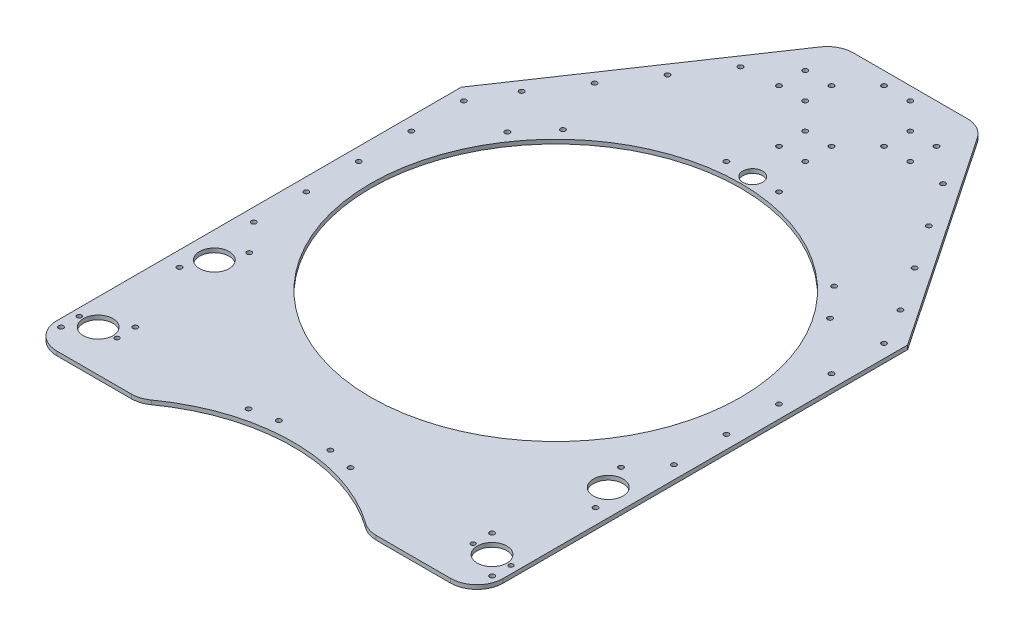
SolidWorks part; units mm, degrees
material "Thornel Mat VMA"
ref_plane "Front Plane" through (0, 0, 0) normal (0, 0, 1) x (1, 0, 0)
ref_plane "Top Plane" through (0, 0, 0) normal (0, 1, 0) x (1, 0, 0)
ref_plane "Right Plane" through (0, 0, 0) normal (1, 0, 0) x (0, 0, -1)
sketch "Sketch1" plane through (0, 0, 0) normal (0, 1, 0) x (1, 0, 0)
  line L1 (-215.9, 342.9) -> (215.9, 342.9)
  line L2 (-215.9, 342.9) -> (-215.9, -342.9)
  line L3 (-215.9, -342.9) -> (215.9, -342.9)
  line L4 (215.9, 342.9) -> (215.9, -342.9)
  line L5 (-215.9, 342.9) -> (215.9, -342.9) construction
  line L6 (-215.9, -342.9) -> (215.9, 342.9) construction
  point P0 (0, 0)
  dimension "D1" = 431.8
  dimension "D2" = 685.8
extrude "Boss-Extrude1" add sketch "Sketch1" along normal blind 4
sketch "Sketch2" plane through (0, 4, 0) normal (0, 1, 0) x (1, 0, 0)
  line L0 (0, -342.9) -> (0, 342.9) construction
  line L1 (-215.9, -342.9) -> (215.9, -342.9) construction
  line L2 (215.9, 342.9) -> (-215.9, 342.9) construction
  line L3 (-215.9, 342.9) -> (-215.9, -342.9) construction
  line L4 (-208.4605, -320.8555) -> (-190.5, -302.895) construction
  line L5 (-193.1461, -302.895) -> (-215.9, -302.895) construction
  line L6 (190.5, -215.9) -> (190.5, -165.1) construction
  line L7 (190.5, -190.5) -> (201.2345, -213.5202) construction
  line L8 (201.2345, -213.5202) -> (179.7655, -167.4798) construction
  line L9 (-208.4605, -320.8555) -> (-172.5395, -284.9345) construction
  circle A0 centre (-190.5, -302.895) radius 14.3129
  circle A1 centre (-190.5, -190.5) radius 14.3129
  circle A3 centre (190.5, -190.5) radius 14.3129
  circle A4 centre (190.5, -190.5) radius 25.4 construction
  circle A5 centre (-190.5, -190.5) radius 25.4 construction
  circle A6 centre (201.2345, -213.5202) radius 2.3812
  circle A7 centre (179.7655, -167.4798) radius 2.3813
  circle A10 centre (-190.5, -302.895) radius 25.4 construction
  circle A11 centre (-208.4605, -320.8555) radius 2.3813
  circle A15 centre (-172.5395, -284.9345) radius 2.3813
  circle A16 centre (172.5395, -284.9345) radius 2.3813
  circle A17 centre (208.4605, -320.8555) radius 2.3813
  circle A18 centre (190.5, -302.895) radius 14.3129
  circle A19 centre (-179.7655, -167.4798) radius 2.3813
  circle A20 centre (-201.2345, -213.5202) radius 2.3813
  circle A21 centre (208.788, -302.895) radius 2.159
  circle A22 centre (172.212, -302.895) radius 2.159
  circle A23 centre (-172.212, -302.895) radius 2.159
  circle A24 centre (-208.788, -302.895) radius 2.159
  point P33 (-190.5, -304.8)
  point P34 (-189.5475, -303.8475)
  point P48 (190.5, -302.895)
  dimension "D1" = 28.6258
  dimension "D2" = 28.6258
  dimension "D6" = 50.8
  dimension "D7" = 50.8
  dimension "D8" = 4.7625
  dimension "D9" = 4.7625
  dimension "D10" = 18.288
  dimension "D11" = 4.318
  dimension "D12" = 50.8
  dimension "D13" = 4.7625
  dimension "D3" = 40.005
  dimension "D4" = 112.395
  dimension "D5" = 25.4
  dimension "D15" = 45
  dimension "D16" = 25
  dimension "D14" = 2
  dimension "D17" = 2
extrude "Cut-Extrude1" cut sketch "Sketch2" against normal through all
sketch "Sketch3" plane through (0, 0, 0) normal (0, -1, 0) x (-1, 0, 0)
  line L1 (29.8706, 270.2084) -> (-24.7394, 270.2084)
  line L2 (29.8706, 270.2084) -> (29.8706, 216.2334)
  line L3 (29.8706, 216.2334) -> (-24.7394, 216.2334)
  line L4 (-24.7394, 270.2084) -> (-24.7394, 216.2334)
  line L5 (29.8706, 270.2084) -> (-24.7394, 216.2334) construction
  line L6 (29.8706, 216.2334) -> (-24.7394, 270.2084) construction
  point P0 (2.5656, 243.2209)
  dimension "D1" = 53.975
  dimension "D2" = 54.61
extrude "Boss-Extrude2" [suppressed] add sketch "Sketch3" along normal blind 203.2
fillet "Fillet1" [suppressed] radius 20.32
sketch "Sketch4" [suppressed] plane through (0, -203.2, 0) normal (0, -1, 0) x (-1, 0, 0)
  line L0 (-24.7394, 216.2334) -> (29.8706, 216.2334) construction
  line L1 (26.6956, 267.0334) -> (-21.5644, 267.0334)
  line L2 (26.6956, 267.0334) -> (26.6956, 219.4084)
  line L3 (26.6956, 219.4084) -> (-21.5644, 219.4084)
  line L4 (-21.5644, 267.0334) -> (-21.5644, 219.4084)
  line L5 (26.6956, 267.0334) -> (-21.5644, 219.4084) construction
  line L6 (26.6956, 219.4084) -> (-21.5644, 267.0334) construction
  line L7 (29.8706, 270.2084) -> (-24.7394, 270.2084) construction
  line L8 (29.8706, 216.2334) -> (29.8706, 270.2084) construction
  line L9 (-24.7394, 270.2084) -> (-24.7394, 216.2334) construction
  point P0 (2.5656, 243.2209)
  dimension "D1" = 3.175
  dimension "D2" = 3.175
  dimension "D3" = 3.175
  dimension "D4" = 3.175
extrude "Cut-Extrude2" [suppressed] cut sketch "Sketch4" against normal blind 203.2
sketch "Sketch5" [suppressed] plane through (-29.8706, 0, 0) normal (-1, 0, 0) x (0, 0, 1)
  line L0 (-216.2334, -203.2) -> (-216.2334, 0) construction
  line L1 (-216.2334, -203.2) -> (-270.2084, -203.2) construction
  circle A0 centre (-243.2209, -184.15) radius 14.2875
  dimension "D1" = 28.575
  dimension "D2" = 26.9875
  dimension "D3" = 19.05
extrude "Cut-Extrude3" [suppressed] cut sketch "Sketch5" against normal blind 203.2
sketch "Sketch6" plane through (0, 4, 0) normal (0, 1, 0) x (1, 0, 0)
  circle A0 centre (0, -50.8) radius 179.07
  dimension "D1" = 358.14
  dimension "D2" = 50.8
extrude "Cut-Extrude4" cut sketch "Sketch6" against normal through all
sketch "Sketch8" plane through (0, 4, 0) normal (0, 1, 0) x (1, 0, 0)
  circle A0 centre (0, 139.7) radius 9.525
  circle A2 centre (0, 139.7) radius 25.4 construction
  circle A3 centre (25.4, 139.7) radius 2.3813
  circle A4 centre (-25.4, 139.7) radius 2.3813
  dimension "D1" = 19.05
  dimension "D3" = 50.8
  dimension "D4" = 4.7625
  dimension "D5" = 4.7625
  dimension "D2" = 139.7
extrude "Cut-Extrude6" cut sketch "Sketch8" against normal through all
fillet "Fillet2" radius 25.4 2 edges at (215.9, 2, 342.9) (-215.9, 2, 342.9)
sketch "Sketch10" plane through (0, 4, 0) normal (0, 1, 0) x (1, 0, 0)
  line L0 (-215.9, 342.9) -> (-215.9, -317.5) construction
  line L1 (215.9, -317.5) -> (215.9, 342.9) construction
  circle A0 centre (-190.5, 215.9) radius 14.3129
  circle A1 centre (190.5, 215.9) radius 14.3129
  circle A2 centre (-190.5, 215.9) radius 25.4 construction
  circle A3 centre (190.5, 215.9) radius 25.4 construction
  circle A4 centre (190.5, 190.5) radius 2.3813
  circle A5 centre (190.5, 241.3) radius 2.3813
  circle A6 centre (-190.5, 190.5) radius 2.3813
  circle A7 centre (-190.5, 241.3) radius 2.3813
  circle A8 centre (190.5, -190.5) radius 14.3129 construction
  circle A9 centre (-190.5, -190.5) radius 14.3129 construction
  dimension "D1" = 28.6258
  dimension "D2" = 50.8
  dimension "D3" = 28.6258
  dimension "D4" = 50.8
  dimension "D5" = 4.7625
  dimension "D6" = 4.7625
  dimension "D7" = 4.7625
  dimension "D8" = 4.7625
  dimension "D9" = 25.4
  dimension "D10" = 25.4
  dimension "D11" = 406.4
  dimension "D12" = 406.4
extrude "Cut-Extrude8" [suppressed] cut sketch "Sketch10" against normal through all
sketch "Sketch11" plane through (0, 4, 0) normal (0, 1, 0) x (1, 0, 0)
  line L0 (0, -50.8) -> (156.0485, 58.4663) construction
  line L6 (0, 0) -> (0, 139.7) construction
  circle A0 centre (0, -50.8) radius 179.07
  circle A1 centre (0, -50.8) radius 179.07 construction
  circle A2 centre (0, -50.8) radius 184.15
  circle A3 centre (0, -50.8) radius 215.9
  circle A4 centre (156.0485, 58.4663) radius 2.3813
  circle A5 centre (131.1838, 87.3342) radius 2.3813
  circle A6 centre (0, -50.8) radius 190.5 construction
  circle A7 centre (-131.1838, 87.3342) radius 2.3813
  circle A8 centre (-156.0485, 58.4663) radius 2.3813
  dimension "D1" = 368.3
  dimension "D6" = 431.8
  dimension "D7" = 381
  dimension "D9" = 4.7625
  dimension "D10" = 4.7625
  dimension "D2" = 55
  dimension "D8" = 38.1
extrude "Cut-Extrude9" cut sketch "Sketch11" against normal through all contours A4 | A5 | A7 | A8 region at (156.0485, 4, -58.4663) region at (131.1838, 4, -87.3342) region at (-131.1838, 4, -87.3342) region at (-156.0485, 4, -58.4663)
sketch "Sketch13" plane through (0, 4, 0) normal (0, 1, 0) x (1, 0, 0)
  line L0 (-215.9, 342.9) -> (-215.9, -317.5) construction
  line L1 (215.9, 342.9) -> (-215.9, 342.9) construction
  line L2 (0, -342.9) -> (0, 342.9) construction
  line L3 (-190.5, -342.9) -> (190.5, -342.9) construction
  circle A0 centre (-203.2, 317.5) radius 2.3813
  circle A1 centre (-203.2, 266.7) radius 2.3813
  circle A2 centre (-203.2, 215.9) radius 2.3813
  circle A3 centre (-203.2, 165.1) radius 2.3813
  circle A4 centre (-203.2, 114.3) radius 2.3813
  circle A5 centre (-203.2, 63.5) radius 2.3813
  circle A6 centre (-203.2, 12.7) radius 2.3813
  circle A7 centre (-203.2, -38.1) radius 2.3813
  circle A8 centre (-203.2, -88.9) radius 2.3813
  circle A9 centre (-203.2, -139.7) radius 2.3813
  circle A10 centre (203.2, -139.7) radius 2.3813
  circle A11 centre (203.2, 12.7) radius 2.3813
  circle A12 centre (203.2, 63.5) radius 2.3813
  circle A13 centre (203.2, 114.3) radius 2.3813
  circle A14 centre (203.2, 165.1) radius 2.3813
  circle A15 centre (203.2, 266.7) radius 2.3813
  circle A16 centre (203.2, 317.5) radius 2.3813
  circle A17 centre (-25.4, -330.2) radius 2.4664
  circle A20 centre (-50.8, -330.2) radius 2.3078
  circle A21 centre (50.8, -330.2) radius 2.3078
  circle A22 centre (25.4, -330.2) radius 2.4664
  circle A23 centre (203.2, -88.9) radius 2.3813
  circle A24 centre (203.2, -38.1) radius 2.3813
  circle A25 centre (203.2, 215.9) radius 2.3813
  dimension "D1" = 4.7625
  dimension "D2" = 12.7
  dimension "D3" = 25.4
  dimension "D5" = 25.4
  dimension "D6" = 50.8
  dimension "D7" = 12.7
  dimension "D8" = 12.7
  dimension "D4" = 10
extrude "Cut-Extrude10" cut sketch "Sketch13" against normal through all
sketch "Sketch14" plane through (0, 4, 0) normal (0, 1, 0) x (1, 0, 0)
  line L0 (215.9, -317.5) -> (215.9, 342.9) construction
  line L1 (0, -342.9) -> (0, -229.87) construction
  line L2 (-190.5, -342.9) -> (190.5, -342.9) construction
  circle A0 centre (209.55, -245.745) radius 2.3813
  circle A2 centre (0, -50.8) radius 179.07 construction
  circle A3 centre (-209.55, -245.745) radius 2.3813
  circle A4 centre (190.5, -302.895) radius 14.3129 construction
  dimension "D1" = 57.15
  dimension "D3" = 4.7625
  dimension "D2" = 6.35
extrude "Cut-Extrude11" [suppressed] cut sketch "Sketch14" against normal through all
sketch "Sketch16" plane through (0, 4, 0) normal (0, 1, 0) x (1, 0, 0)
  line L0 (215.9, -317.5) -> (215.9, 342.9) construction
  line L1 (-215.9, 342.9) -> (215.9, 342.9)
  line L2 (-215.9, 342.9) -> (-215.9, 292.1)
  line L3 (-215.9, 292.1) -> (215.9, 292.1)
  line L4 (215.9, 342.9) -> (215.9, 292.1)
  dimension "D1" = 50.8
extrude "Cut-Extrude13" cut sketch "Sketch16" against normal through all
sketch "Sketch17" plane through (0, 0, 0) normal (0, -1, 0) x (-1, 0, 0)
  line L0 (0, -482.6) -> (0, 3.1553) construction
  line L1 (0, -482.6) -> (24.8652, -293.7298) construction
  line L2 (0, -482.6) -> (49.305, -298.5911) construction
  circle A0 centre (0, -482.6) radius 177.8
  circle A1 centre (0, -482.6) radius 190.5 construction
  circle A2 centre (24.8652, -293.7298) radius 2.3813
  circle A3 centre (49.305, -298.5911) radius 2.3813
  circle A4 centre (-24.8652, -293.7298) radius 2.3813
  circle A5 centre (-49.305, -298.5911) radius 2.3813
  dimension "D1" = 355.6
  dimension "D3" = 381
  dimension "D6" = 4.7625
  dimension "D7" = 4.7625
  dimension "D2" = 482.6
  dimension "D4" = 7.5
  dimension "D5" = 15
extrude "Cut-Extrude14" cut sketch "Sketch17" against normal through all
fillet "Fillet3" radius 25.4 2 edges at (109.9852, 2, 342.9) (-109.9852, 2, 342.9)
sketch "Sketch18" plane through (0, 4, 0) normal (0, 1, 0) x (1, 0, 0)
  line L0 (-215.9, 292.1) -> (215.9, 292.1) construction
  line L1 (25.4, 215.9) -> (-25.4, 215.9) construction
  line L2 (25.4, 215.9) -> (25.4, 266.7) construction
  line L3 (25.4, 266.7) -> (-25.4, 266.7) construction
  line L4 (-25.4, 215.9) -> (-25.4, 266.7) construction
  line L5 (25.4, 215.9) -> (-25.4, 266.7) construction
  line L6 (25.4, 266.7) -> (-25.4, 215.9) construction
  line L8 (25.4, 215.9) -> (76.2, 215.9) construction
  line L9 (25.4, 215.9) -> (25.4, 266.7) construction
  line L10 (25.4, 266.7) -> (76.2, 266.7) construction
  line L11 (76.2, 215.9) -> (76.2, 266.7) construction
  circle A0 centre (38.1, 228.6) radius 2.3812
  circle A1 centre (63.5, 228.6) radius 2.3813
  circle A2 centre (63.5, 254) radius 2.3813
  circle A3 centre (38.1, 254) radius 2.3813
  circle A4 centre (-12.7, 177.8) radius 2.3813
  circle A5 centre (-12.7, 203.2) radius 2.3813
  circle A6 centre (12.7, 177.8) radius 2.3813
  circle A7 centre (12.7, 203.2) radius 2.3812
  circle A8 centre (-63.5, 254) radius 2.3812
  circle A9 centre (-38.1, 254) radius 2.3813
  circle A10 centre (-63.5, 228.6) radius 2.3813
  circle A11 centre (-38.1, 228.6) radius 2.3813
  circle A12 centre (12.7, 304.8) radius 2.3812
  circle A13 centre (12.7, 279.4) radius 2.3812
  circle A14 centre (-12.7, 304.8) radius 2.3813
  circle A15 centre (-12.7, 279.4) radius 2.3812
  point P0 (0, 241.3)
  point P45 (0, 241.3)
  dimension "D5" = 4.7625
  dimension "D1" = 50.8
  dimension "D2" = 50.8
  dimension "D3" = 50.8
  dimension "D4" = 12.7
  dimension "D6" = 25.4
  dimension "D9" = 50.8
  dimension "D10" = 4
  dimension "D7" = 2
  dimension "D8" = 2
extrude "Cut-Extrude15" cut sketch "Sketch18" against normal through all
chamfer "Chamfer1" distance 147.32 angle 56 1 edges at (215.9, 2, -292.1) first distance on face at (0, 2, -292.1)
chamfer "Chamfer2" distance 147.32 angle 56 1 edges at (-215.9, 2, -292.1) first distance on face at (-73.66, 2, -292.1)
fillet "Fillet4" radius 25.4 2 edges at (68.58, 2, -292.1) (-68.58, 2, -292.1)
sketch "Sketch19" plane through (0, 4, 0) normal (0, 1, 0) x (1, 0, 0)
  line L0 (-76.1321, 280.9035) -> (-215.9, 73.6891) construction
  line L1 (-55.0746, 292.1) -> (55.0746, 292.1) construction
  line L2 (0, 292.1) -> (0, -304.8) construction
  circle A0 centre (-97.9769, 225.806) radius 2.3813
  circle A2 centre (-126.3839, 183.6909) radius 2.3813
  circle A3 centre (-154.7909, 141.5758) radius 2.3813
  circle A4 centre (-183.1979, 99.4607) radius 2.3813
  arc A5 (103.6505, -338.1375) -> (-103.6505, -338.1375) centre (0, -482.6) ccw construction
  circle A6 centre (183.1979, 99.4607) radius 2.3813
  circle A7 centre (154.7909, 141.5758) radius 2.3813
  circle A8 centre (126.3839, 183.6909) radius 2.3812
  circle A9 centre (97.9769, 225.806) radius 2.3813
  dimension "D1" = 12.7
  dimension "D2" = 4.7625
  dimension "D3" = 66.294
  dimension "D4" = 4
extrude "Cut-Extrude16" cut sketch "Sketch19" against normal through all
